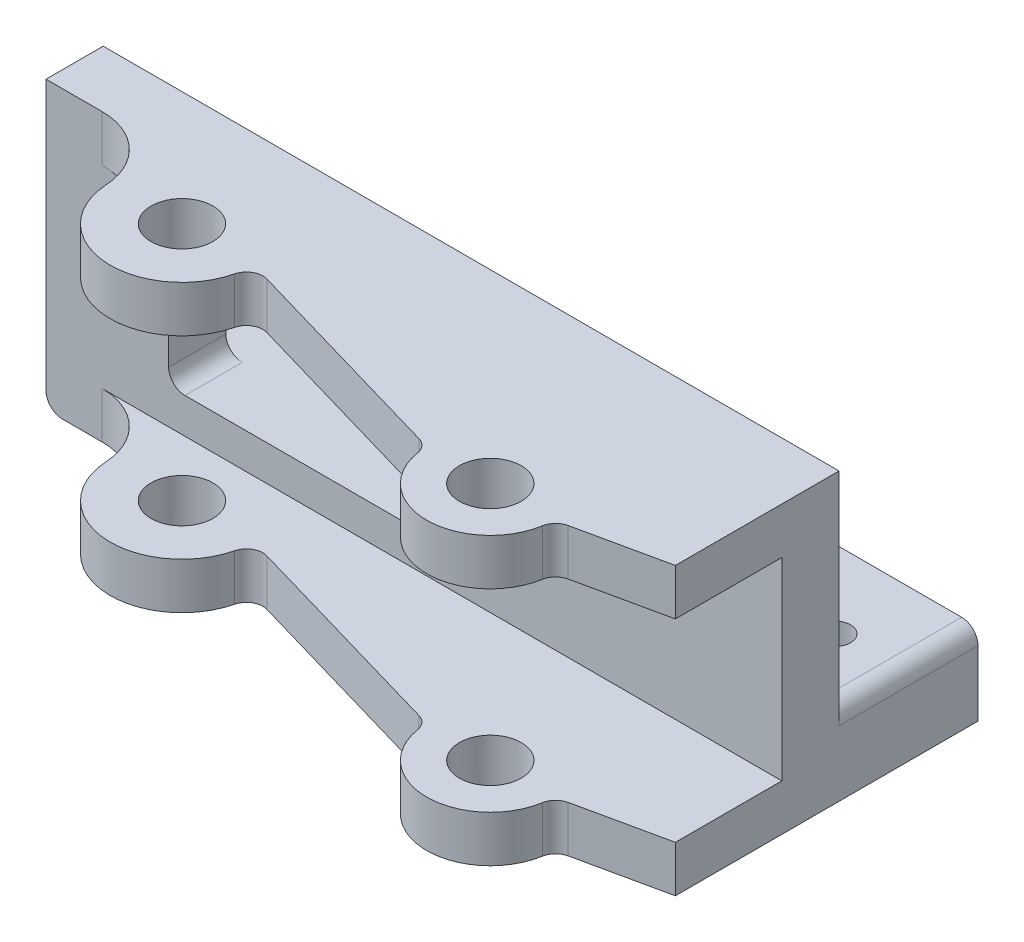
SolidWorks part; units mm, degrees
ref_plane "Front Plane" through (0, 0, 0) normal (0, 0, 1) x (1, 0, 0)
ref_plane "Top Plane" through (0, 0, 0) normal (0, 1, 0) x (1, 0, 0)
ref_plane "Right Plane" through (0, 0, 0) normal (1, 0, 0) x (0, 0, -1)
sketch "Sketch1" plane through (0, 0, 0) normal (0, 0, 1) x (1, 0, 0)
  line L1 (57.15, -22.225) -> (-57.15, -22.225)
  line L2 (57.15, -22.225) -> (57.15, 22.225)
  line L3 (57.15, 22.225) -> (-57.15, 22.225)
  line L4 (-57.15, -22.225) -> (-57.15, 22.225)
  line L5 (57.15, -22.225) -> (-57.15, 22.225) construction
  line L6 (57.15, 22.225) -> (-57.15, -22.225) construction
  point P0 (0, 0)
  dimension "D1" = 44.45
  dimension "D2" = 114.3
extrude "Boss-Extrude1" add sketch "Sketch1" along normal blind 62.23
sketch "Sketch2" plane through (0, 0, 62.23) normal (0, 0, 1) x (1, 0, 0)
  line L0 (-57.15, 22.225) -> (-57.15, -22.225) construction
  line L1 (57.15, -15.025) -> (-57.15, -15.025)
  line L2 (57.15, -15.025) -> (57.15, 15.025)
  line L3 (57.15, 15.025) -> (-57.15, 15.025)
  line L4 (-57.15, -15.025) -> (-57.15, 15.025)
  line L5 (57.15, -15.025) -> (-57.15, 15.025) construction
  line L6 (57.15, 15.025) -> (-57.15, -15.025) construction
  line L7 (57.15, 22.225) -> (-57.15, 22.225) construction
  point P0 (0, 0)
  dimension "D1" = 7.2
extrude "Cut-Extrude2" cut sketch "Sketch2" against normal blind 31.75
sketch "Sketch3" plane through (0, 0, 0) normal (0, 0, -1) x (-1, 0, 0)
  line L0 (-57.15, -22.225) -> (-57.15, 22.225) construction
  line L1 (57.15, 22.225) -> (-57.15, 22.225)
  line L2 (57.15, 22.225) -> (57.15, -9.525)
  line L3 (57.15, -9.525) -> (-57.15, -9.525)
  line L4 (-57.15, 22.225) -> (-57.15, -9.525)
  line L5 (57.15, -22.225) -> (-57.15, -22.225) construction
  dimension "D1" = 12.7
extrude "Cut-Extrude3" cut sketch "Sketch3" against normal blind 21.59
sketch "Sketch5" plane through (0, -22.225, 0) normal (0, -1, 0) x (1, 0, 0)
  line L0 (-3.81, 12.06) -> (46.99, 12.06) construction
  line L1 (57.15, 21.59) -> (-57.15, 21.59) construction
  line L2 (57.15, 62.23) -> (57.15, 0) construction
  circle A0 centre (-3.81, 12.06) radius 2.415
  circle A1 centre (46.99, 12.06) radius 2.415
  dimension "D3" = 4.83
  dimension "D4" = 10.16
  dimension "D1" = 9.53
  dimension "D2" = 50.8
extrude "Cut-Extrude4" cut sketch "Sketch5" against normal blind 25.4
sketch "Sketch7" plane through (0, -22.225, 0) normal (0, -1, 0) x (1, 0, 0)
  line L0 (57.15, 62.23) -> (57.15, 0) construction
  line L1 (-57.15, 0) -> (57.15, 0) construction
  circle A0 centre (31.75, 50.36) radius 4.8
  circle A1 centre (-27.14, 39.37) radius 4.8
  dimension "D1" = 9.6
  dimension "D2" = 25.4
  dimension "D3" = 39.37
  dimension "D4" = 9.6
  dimension "D5" = 58.89
  dimension "D6" = 10.99
extrude "Cut-Extrude6" cut sketch "Sketch7" against normal up to surface (44.45 mm away) up to face at (0, 22.225, 41.91)
sketch "Sketch9" plane through (0, 0, 30.48) normal (0, 0, 1) x (1, 0, 0)
  line L5 (57.15, 15.025) -> (-57.15, 15.025) construction
  line L6 (-38.1, 15.025) -> (6.35, 15.025)
  line L7 (-38.1, 15.025) -> (-38.1, -15.025)
  line L8 (-38.1, -15.025) -> (6.35, -15.025)
  line L9 (6.35, 15.025) -> (6.35, -15.025)
  line L10 (-57.15, -15.025) -> (57.15, -15.025) construction
  line L11 (-57.15, 15.025) -> (-57.15, -15.025) construction
  line L12 (57.15, -15.025) -> (57.15, 15.025) construction
  dimension "D1" = 50.8
  dimension "25in" = 19.05
extrude "Cut-Extrude7" cut sketch "Sketch9" against normal through all both and the other way through all
sketch "Sketch16" plane through (0, -22.225, 0) normal (0, -1, 0) x (1, 0, 0)
  line L1 (-38.1, 30.48) -> (-57.15, 30.48) construction
  line L8 (-57.15, 62.23) -> (57.15, 62.23)
  line L9 (57.15, 62.23) -> (57.15, 47.0103)
  line L10 (57.15, 62.23) -> (57.15, 0) construction
  line L11 (-15.99, 39.37) -> (21.87, 50.36)
  line L12 (41.63, 50.36) -> (57.15, 47.0103)
  line L13 (-48.4121, 30.48) -> (-57.15, 30.48)
  line L15 (-57.15, 30.48) -> (-57.15, 62.23)
  arc A2 (41.63, 50.36) -> (21.87, 50.36) centre (31.75, 50.36) ccw
  arc A3 (-15.99, 39.37) -> (-38.2702, 40.0345) centre (-27.14, 39.37) ccw
  circle A4 centre (-27.14, 39.37) radius 4.8 construction
  circle A5 centre (31.75, 50.36) radius 4.8 construction
  arc A6 (-48.4121, 30.48) -> (-38.2702, 40.0345) centre (-48.4121, 40.64) ccw
  dimension "D1" = 6.35
  dimension "D2" = 5.08
  dimension "D3" = 10.16
extrude "Cut-Extrude8" cut sketch "Sketch16" against normal through all
fillet "Fillet1" radius 2.54 6 edges at (21.87, 18.625, 50.36) (41.63, -18.625, 50.36) (41.63, 18.625, 50.36) (-15.99, 18.625, 39.37) (-15.99, -18.625, 39.37) (21.87, -18.625, 50.36)
sketch "Sketch14" plane through (6.35, 0, 0) normal (-1, 0, 0) x (0, 0, 1)
  line L0 (0, -15.025) -> (30.48, -15.025) construction
  line L1 (21.59, -9.525) -> (0, -9.525)
  line L2 (21.59, -9.525) -> (21.59, -15.025)
  line L3 (21.59, -15.025) -> (0, -15.025)
  line L4 (0, -9.525) -> (0, -15.025)
extrude "Boss-Extrude2" add sketch "Sketch14" along normal up to next
sketch "Sketch17" plane through (0, 0, 21.59) normal (0, 0, 1) x (1, 0, 0)
  line L1 (6.35, -15.025) -> (-38.1, -15.025)
  line L2 (6.35, -15.025) -> (6.35, -9.525)
  line L3 (6.35, -9.525) -> (-38.1, -9.525)
  line L4 (-38.1, -15.025) -> (-38.1, -9.525)
extrude "Boss-Extrude3" add sketch "Sketch17" along normal up to surface (8.89 mm away) up to face at (31.75, 0, 30.48)
sketch "Sketch18" plane through (-57.15, 0, 0) normal (-1, 0, 0) x (0, 0, 1)
  line L0 (30.48, 22.225) -> (30.48, -22.225) construction
  line L1 (21.59, 22.225) -> (30.48, 22.225)
  line L2 (21.59, 22.225) -> (21.59, -22.225)
  line L3 (21.59, -22.225) -> (30.48, -22.225)
  line L4 (30.48, 22.225) -> (30.48, -22.225)
  line L5 (21.59, 22.225) -> (30.48, -22.225) construction
  line L6 (21.59, -22.225) -> (30.48, 22.225) construction
  line L7 (30.48, -22.225) -> (0, -22.225) construction
  line L8 (21.59, -9.525) -> (21.59, 22.225) construction
  line L9 (30.48, 22.225) -> (21.59, 22.225) construction
  point P0 (26.035, 0)
sketch "Sketch20" plane through (0, 0, 21.59) normal (0, 0, -1) x (-1, 0, 0)
  line L0 (38.1, 15.025) -> (38.1, -9.525) construction
  line L1 (38.1, 38.1) -> (88.9, 38.1)
  line L2 (38.1, 38.1) -> (38.1, -38.1)
  line L3 (38.1, -38.1) -> (88.9, -38.1)
  line L4 (88.9, 38.1) -> (88.9, -38.1)
  line L5 (38.1, 38.1) -> (88.9, -38.1) construction
  line L6 (38.1, -38.1) -> (88.9, 38.1) construction
  point P0 (63.5, 0)
  point P9 (88.9, 0)
  dimension "D1" = 76.2
  dimension "D2" = 50.8
sketch "Sketch21" plane through (0, 0, 30.48) normal (0, 0, 1) x (1, 0, 0)
  line L0 (-54.61, -20.32) -> (-54.61, -19.685)
  line L13 (-54.61, 19.685) -> (-54.61, -19.685)
  line L14 (-54.61, 19.685) -> (-54.61, -19.685)
  line L16 (-50.9521, -12.485) -> (-40.64, -12.485)
  line L17 (-40.64, -12.485) -> (-40.64, -12.065)
  line L34 (-54.61, -19.685) -> (-50.9521, -19.685)
  line L35 (-50.9521, -19.685) -> (-50.9521, -12.485)
  line L36 (-50.9521, -12.485) -> (54.61, -12.485)
  line L37 (54.61, -12.485) -> (54.61, 12.485)
  line L38 (54.61, 12.485) -> (8.89, 12.485)
  line L39 (8.89, 12.485) -> (8.89, -12.065)
  line L40 (8.89, -12.065) -> (-40.64, -12.065)
  line L41 (-40.64, -12.065) -> (-40.64, 12.485)
  line L42 (-40.64, 12.485) -> (-50.9521, 12.485)
  line L43 (-50.9521, 12.485) -> (-50.9521, 19.685)
  line L44 (-50.9521, 19.685) -> (-54.61, 19.685)
  line L50 (-54.61, -19.685) -> (-50.9521, -19.685)
  line L51 (-50.9521, -19.685) -> (-50.9521, -12.485)
  line L57 (-40.64, -12.065) -> (-40.64, 12.485)
  line L58 (-40.64, 12.485) -> (-50.9521, 12.485)
  line L59 (-50.9521, 12.485) -> (-50.9521, 19.685)
  line L60 (-50.9521, 19.685) -> (-54.61, 19.685)
  dimension "D1" = 2.54
fillet "Fillet6" radius 2.54 7 edges at (6.35, -9.525, 26.035) (6.35, 15.025, 26.035) (-38.1, 15.025, 26.035) (-38.1, -9.525, 26.035) (57.15, -9.525, 10.795) (-57.15, -9.525, 10.795) (-57.15, -22.225, 15.24)
